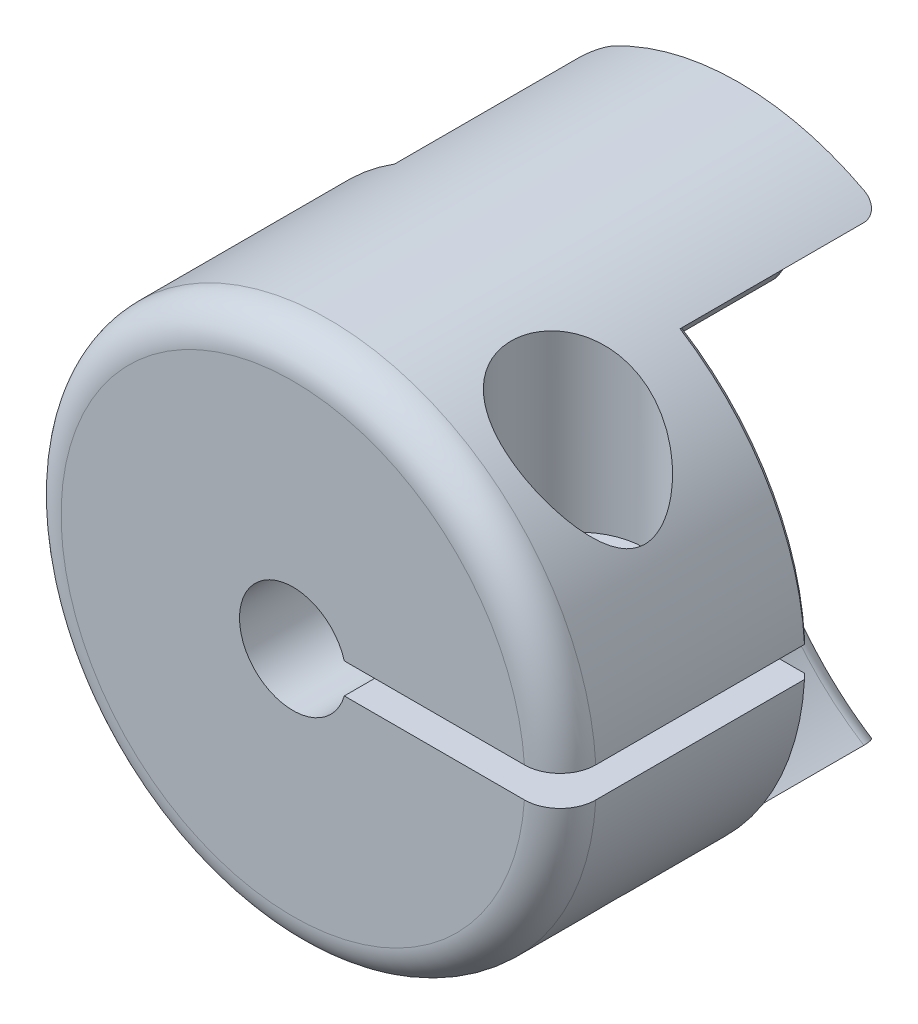
SolidWorks part; units mm, degrees
ref_plane "Front Plane" through (0, 0, 0) normal (0, 0, 1) x (1, 0, 0)
ref_plane "Top Plane" through (0, 0, 0) normal (0, 1, 0) x (1, 0, 0)
ref_plane "Right Plane" through (0, 0, 0) normal (1, 0, 0) x (0, 0, -1)
sketch "Sketch1" plane through (0, 0, 0) normal (0, 0, 1) x (1, 0, 0)
  circle A0 centre (0, 0) radius 15
  circle A1 centre (0, 0) radius 3
  dimension "D1" = 30
  dimension "D2" = 6
extrude "Boss-Extrude1" add sketch "Sketch1" along normal mid plane 25
sketch "Sketch2" plane through (0, 0, -12.5) normal (0, 0, -1) x (-1, 0, 0)
  line L0 (0, 0) -> (-16, 0) construction
  line L1 (0, 30.9567) -> (0, 22.4384) construction
  circle A0 centre (-16, 0) radius 15
  circle A1 centre (16, 0) radius 15
  dimension "D2" = 30
  dimension "D1" = 16
extrude "Cut-Extrude1" cut sketch "Sketch2" against normal blind 11
sketch "Sketch3" plane through (0, 0, -12.5) normal (0, 0, -1) x (-1, 0, 0)
  line L0 (0, 0) -> (5.5, 0) construction
  line L1 (7.9547, -0.85) -> (11, -0.85)
  line L2 (0, -0.85) -> (0, 0.85) construction
  line L3 (7.9547, 0.85) -> (11, 0.85)
  line L4 (11, -0.85) -> (11, 0.85)
  line L5 (0, -0.85) -> (11, 0.85) construction
  line L6 (0, 0.85) -> (11, -0.85) construction
  arc A0 (7.9547, 0.85) -> (7.9547, -0.85) centre (0, 0) ccw
  point P3 (5.5, 0)
  dimension "D1" = 16
  dimension "D2" = 1.7
  dimension "D3" = 11
extrude "Cut-Extrude2" cut sketch "Sketch3" against normal blind 12
sketch "Sketch6" plane through (0, -0.85, 0) normal (0, 1, 0) x (1, 0, 0)
  line L0 (-11, 0.5) -> (15, -25.5)
  line L1 (-11, 0.5) -> (15, 0.5) construction
  line L2 (15, 0.5) -> (15, -25.5)
  line L3 (15, -12.5) -> (15, 1.5) construction
  line L4 (15, 0.5) -> (15, 1.5)
  line L5 (15, 1.5) -> (-11, 1.5)
  line L6 (-11, 1.5) -> (-11, 0.5)
  dimension "D1" = 45
extrude "Cut-Extrude3" cut sketch "Sketch6" along normal up to surface (1.7 mm away) up to face at (-9.4774, 0.85, -1)
sketch "Sketch7" plane through (0, 0, 0) normal (0, 1, 0) x (1, 0, 0)
  line L0 (-15, -12.5) -> (14.9759, -12.5) construction
  line L1 (14.9759, -12.5) -> (14.9759, 1.5) construction
  circle A0 centre (8.9759, -5.5) radius 2
  dimension "D1" = 4
  dimension "D2" = 7
  dimension "D3" = 6
extrude "Cut-Extrude4" cut sketch "Sketch7" against normal through all both and the other way through all
sketch "Sketch8" plane through (0, -0.85, 0) normal (0, 1, 0) x (1, 0, 0)
  circle A0 centre (8.9759, -5.5) radius 3.75
  dimension "D1" = 7.5
extrude "Cut-Extrude5" cut sketch "Sketch8" along normal through all from offset 4.85
fillet "Fillet1" radius 2 1 edges at (-15, 0, 12.5)
fillet "Fillet2" radius 1 6 edges at (0, 8, -12.5) (5.1605, 10.3685, -12.5) (-5.1605, 10.3685, -12.5) (-5.1605, -10.3685, -12.5) (0, -8, -12.5) (5.1605, -10.3685, -12.5)
chamfer "Chamfer1" distance 0.3 angle 45 3 edges at (12.9233, -7.6151, -1.5) (12.9233, 7.6151, -1.5) (-15, 0, -1.5)
equation "\"inner diameter\" = 6mm"
equation "\"D2@Sketch1\"=\"inner diameter\""
